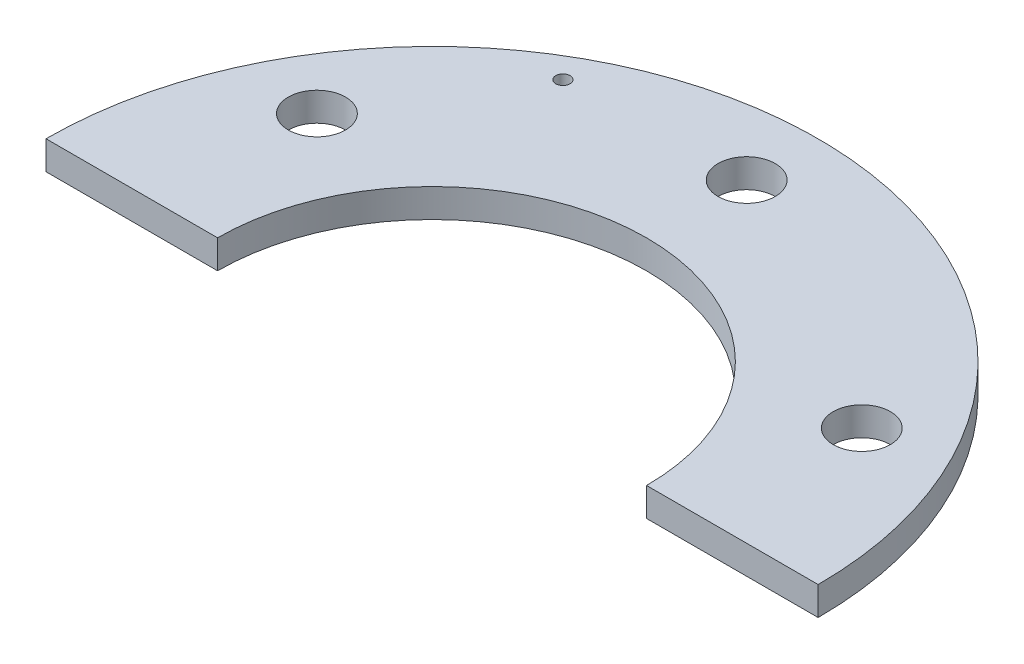
SolidWorks part; units mm, degrees
material "ABS"
ref_plane "Front Plane" through (0, 0, 0) normal (0, 0, 1) x (1, 0, 0)
ref_plane "Top Plane" through (0, 0, 0) normal (0, 1, 0) x (1, 0, 0)
ref_plane "Right Plane" through (0, 0, 0) normal (1, 0, 0) x (0, 0, -1)
sketch "Sketch1" plane through (0, 0, 0) normal (0, 1, 0) x (1, 0, 0)
  circle A0 centre (0, 0) radius 13.5
  dimension "D1" = 27
extrude "Boss-Extrude1" add sketch "Sketch1" along normal blind 1
sketch "Sketch19" plane through (0, 1, 0) normal (0, 1, 0) x (1, 0, 0)
  circle A0 centre (0, 11) radius 1
  circle A1 centre (9.5263, 5.5) radius 1
  circle A2 centre (9.5263, -5.5) radius 1
  circle A3 centre (0, -11) radius 1
  circle A4 centre (-9.5263, -5.5) radius 1
  circle A5 centre (-9.5263, 5.5) radius 1
  point P13 (0, 0)
  dimension "D1" = 2
  dimension "D2" = 11
  dimension "D3" = 6
extrude "Cut-Extrude1" cut sketch "Sketch19" against normal through all both and the other way through all
sketch "Sketch20" plane through (0, 1, 0) normal (0, 1, 0) x (1, 0, 0)
  circle A0 centre (0, 0) radius 7.5
  dimension "D1" = 15
extrude "Cut-Extrude2" cut sketch "Sketch20" against normal through all both and the other way through all
sketch "Sketch21" plane through (0, 0, 0) normal (0, 0, 1) x (1, 0, 0)
  line L1 (-36.7533, 32.3113) -> (29.1209, 32.3113)
  line L2 (-36.7533, 32.3113) -> (-36.7533, -19.668)
  line L3 (-36.7533, -19.668) -> (29.1209, -19.668)
  line L4 (29.1209, 32.3113) -> (29.1209, -19.668)
extrude "Cut-Extrude3" cut sketch "Sketch21" along normal through all
sketch "Sketch22" plane through (0, 1, 0) normal (0, 1, 0) x (1, 0, 0)
  line L0 (-9.5263, 5.5) -> (0, 11)
  line L1 (-6.25, 10.8253) -> (0, 0) construction
  circle A0 centre (-6.25, 10.8253) radius 0.25
  point P7 (-4.7631, 8.25)
  dimension "D1" = 0.5
  dimension "D2" = 12.5
  dimension "D3" = 0
extrude "Cut-Extrude4" cut sketch "Sketch22" against normal through all both and the other way through all contours L0 A0 | L0 L1 A0 | L1 L0 A0 region at (-6.25, 1, -10.8253)
